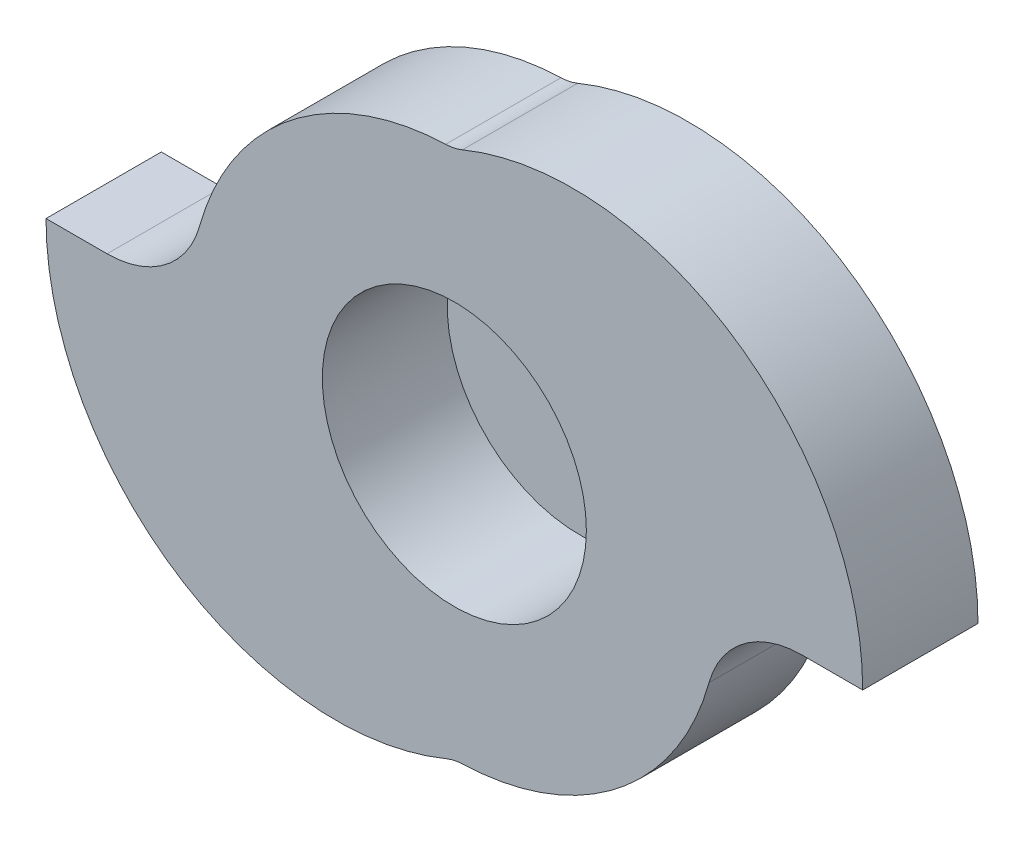
SolidWorks part; units mm, degrees
ref_plane "Front Plane" through (0, 0, 0) normal (0, 0, 1) x (1, 0, 0)
ref_plane "Top Plane" through (0, 0, 0) normal (0, 1, 0) x (1, 0, 0)
ref_plane "Right Plane" through (0, 0, 0) normal (1, 0, 0) x (0, 0, -1)
sketch "Sketch1" plane through (0, 0, 0) normal (0, 0, 1) x (1, 0, 0)
  line L0 (-27.5, 0) -> (-42.5, 0)
  line L1 (27.5, 0) -> (42.5, 0)
  arc A0 (0, 27.5) -> (-27.5, 0) centre (0, 0) ccw
  arc A1 (42.5, 0) -> (0, 27.5) centre (12.3529, 0) ccw
  arc A2 (-42.5, 0) -> (0, -27.5) centre (-12.3529, 0) ccw
  arc A3 (0, -27.5) -> (27.5, 0) centre (0, 0) ccw
  circle A4 centre (0, 0) radius 2.5
  dimension "D1" = 15
  dimension "D3" = 55
  dimension "D2" = 15
extrude "Boss-Extrude1" add sketch "Sketch1" along normal blind 12 contours A3 L1 A1 A0 L0 A2
sketch "Sketch2" plane through (0, 0, 12) normal (0, 0, 1) x (1, 0, 0)
  circle A0 centre (0, 0) radius 16.115
  dimension "D1" = 32.23
extrude "Boss-Extrude2" add sketch "Sketch2" against normal blind 25
sketch "Sketch3" plane through (0, 0, 12) normal (0, 0, 1) x (1, 0, 0)
  circle A0 centre (0, 0) radius 13.74
extrude "Cut-Extrude2" cut sketch "Sketch3" along direction (0, 0, 1) on the side against the normal offset from surface (13 mm away) 13 up to face at (0, 0, 12)
sketch "Sketch4" plane through (0, 0, -13) normal (0, 0, -1) x (-1, 0, 0)
  circle A0 centre (0, 0) radius 2.5
extrude "Cut-Extrude3" cut sketch "Sketch4" along direction (0, 0, 1) on the side against the normal offset from surface (17 mm away) 5 up to face at (13.74, 0, -1) offset beyond the face yes
fillet "Fillet1" radius 5 1 edges at (0, 27.5, 6)
fillet "Fillet2" radius 10 1 edges at (-27.5, 0, 6)
fillet "Fillet3" radius 10 1 edges at (27.5, 0, 6)
fillet "Fillet5" radius 5 1 edges at (0, -27.5, 6)
fillet "Fillet6" radius 5 1 edges at (16.115, 0, 0)
